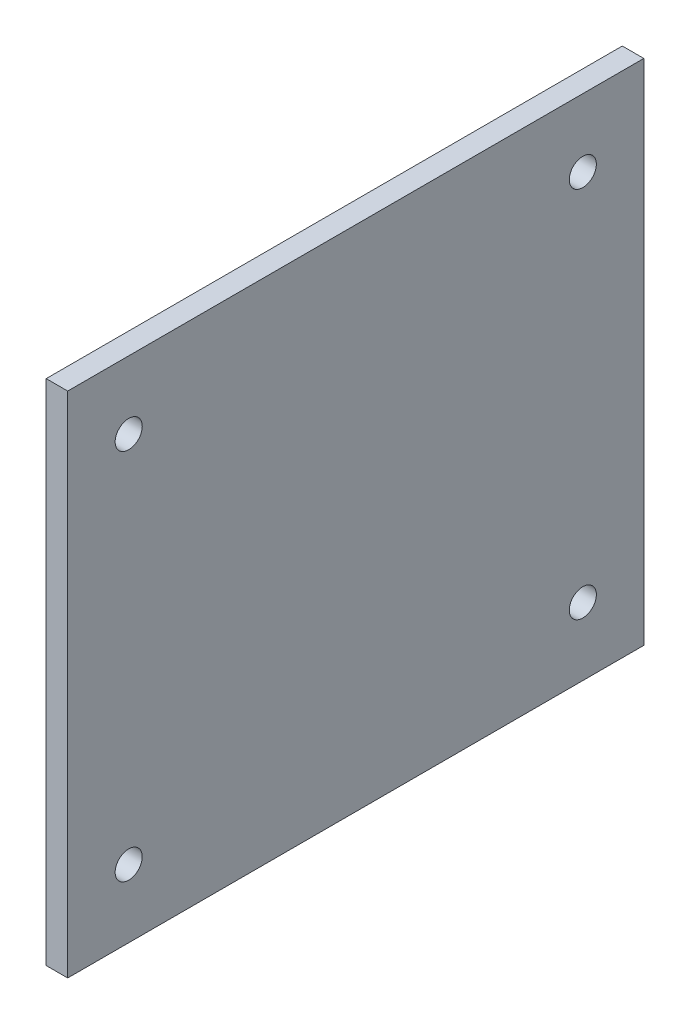
SolidWorks part; units mm, degrees
ref_plane "Front Plane" through (0, 0, 0) normal (0, 0, 1) x (1, 0, 0)
ref_plane "Top Plane" through (0, 0, 0) normal (0, 1, 0) x (1, 0, 0)
ref_plane "Right Plane" through (0, 0, 0) normal (1, 0, 0) x (0, 0, -1)
sketch "Sketch1" plane through (0, 0, 0) normal (1, 0, 0) x (0, 0, -1)
  line L0 (0, 37.5) -> (85, 37.5) construction
  line L1 (0, 0) -> (85, 0)
  line L2 (0, 0) -> (0, 75)
  line L3 (0, 75) -> (85, 75)
  line L4 (85, 0) -> (85, 75)
  line L5 (42.5, 75) -> (42.5, 0) construction
  circle A0 centre (9, 65) radius 2
  circle A1 centre (9, 10) radius 2
  circle A2 centre (76, 10) radius 2
  circle A3 centre (76, 65) radius 2
  dimension "D5" = 4
  dimension "D1" = 75
  dimension "D2" = 85
  dimension "D3" = 10
  dimension "D4" = 9
extrude "Boss-Extrude1" add sketch "Sketch1" along normal blind 3.175
